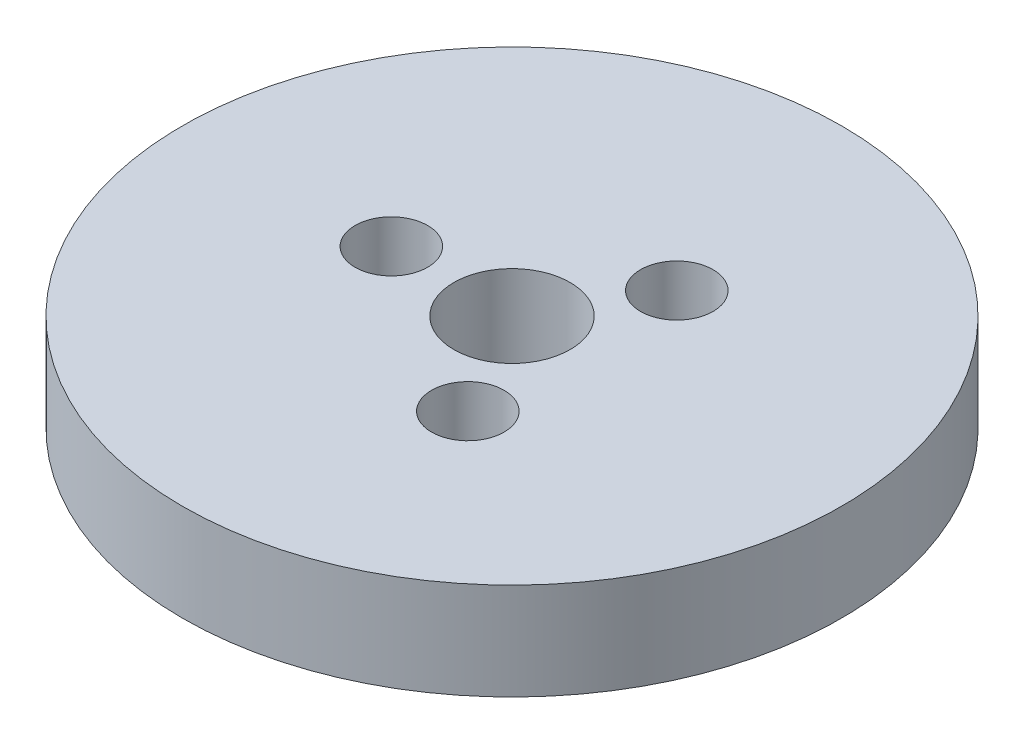
SolidWorks part; units mm, degrees
ref_plane "Front Plane" through (0, 0, 0) normal (0, 0, 1) x (1, 0, 0)
ref_plane "Top Plane" through (0, 0, 0) normal (0, 1, 0) x (1, 0, 0)
ref_plane "Right Plane" through (0, 0, 0) normal (1, 0, 0) x (0, 0, -1)
sketch "Sketch1" plane through (0, 0, 0) normal (0, 1, 0) x (1, 0, 0)
  circle A0 centre (0, 0) radius 85
  dimension "FLANGE_OD" = 170
extrude "Boss-Extrude1" add sketch "Sketch1" along normal blind 25
sketch "Sketch2" plane through (0, 0, 0) normal (0, 1, 0) x (1, 0, 0)
  circle A0 centre (0, 0) radius 15
  dimension "BORE_D" = 30
extrude "Cut-Extrude1" cut sketch "Sketch2" along normal through all
sketch "Sketch3" plane through (0, 25, 0) normal (0, 1, 0) x (1, 0, 0)
  circle A0 centre (0, 0) radius 31.118 construction
  circle A1 centre (-31.118, 0) radius 9.3526
  dimension "BOLT_D" = 18.7053
  dimension "BOLT_PCD" = 62.2361
extrude "Cut-Extrude2" cut sketch "Sketch3" against normal blind 17.5716
pattern_circular "CirPattern1" count 3 over 360 about axis through (0, 0, 0) along (0, 1, 0) of "Cut-Extrude2"
